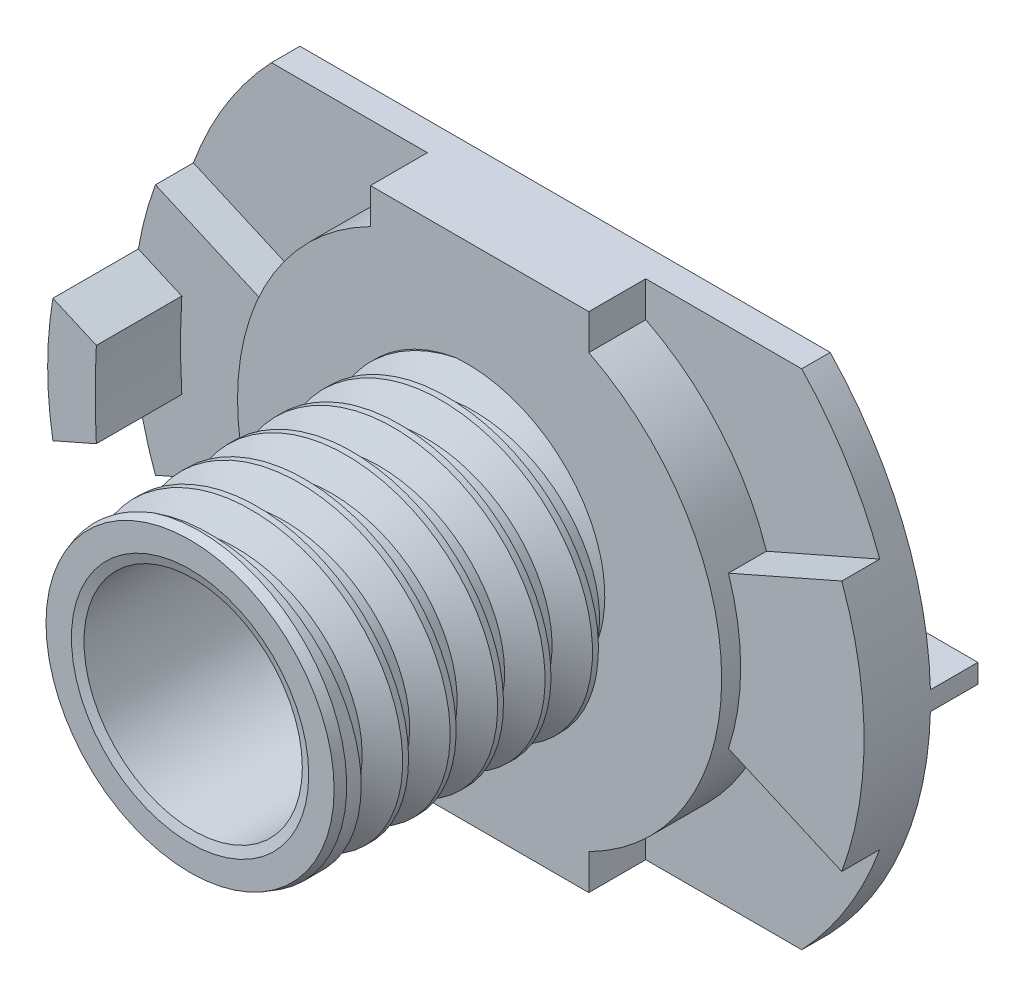
SolidWorks part; units mm, degrees
ref_plane "Front Plane" through (0, 0, 0) normal (0, 0, 1) x (1, 0, 0)
ref_plane "Top Plane" through (0, 0, 0) normal (0, 1, 0) x (1, 0, 0)
ref_plane "Right Plane" through (0, 0, 0) normal (1, 0, 0) x (0, 0, -1)
sketch "Sketch1" plane through (0, 0, 0) normal (0, 0, 1) x (1, 0, 0)
  line L1 (-5.5857, 5.3) -> (5.5857, 5.3)
  line L3 (-5.5857, -5.3) -> (5.5857, -5.3)
  line L5 (-5.5857, 5.3) -> (5.5857, -5.3) construction
  line L6 (-5.5857, -5.3) -> (5.5857, 5.3) construction
  arc A0 (-5.5857, 5.3) -> (-5.5857, -5.3) centre (0, 0) ccw
  arc A1 (5.5857, -5.3) -> (5.5857, 5.3) centre (0, 0) ccw
  dimension "D1" = 15.4
  dimension "D2" = 10.6
extrude "Boss-Extrude1" add sketch "Sketch1" along normal mid plane 0.6
sketch "Sketch2" plane through (0, 0, 0) normal (0, 0, 1) x (1, 0, 0)
  line L0 (5.5857, 5.3) -> (-5.5857, 5.3) construction
  line L1 (-2.3, 5.3) -> (2.3, 5.3)
  line L2 (-2.3, 5.3) -> (-2.3, 4.5519)
  line L4 (2.3, 5.3) -> (2.3, 4.5519)
  line L5 (-5.5857, -5.3) -> (5.5857, -5.3) construction
  line L6 (2.3, -5.3) -> (-2.3, -5.3)
  line L7 (2.3, -5.3) -> (2.3, -4.5519)
  line L9 (-2.3, -5.3) -> (-2.3, -4.5519)
  arc A0 (-2.3, 4.5519) -> (-2.3, -4.5519) centre (0, 0) ccw
  arc A1 (2.3, -4.5519) -> (2.3, 4.5519) centre (0, 0) ccw
  point P1 (0, 5.3)
  point P17 (0, -5.3)
  dimension "D1" = 10.2
  dimension "D2" = 4.6
extrude "Boss-Extrude2" add sketch "Sketch2" along normal blind 1.2 from surface starting at face at (0, 0, 0.3)
sketch "Sketch3" plane through (0, 0, 0) normal (0, 0, 1) x (1, 0, 0)
  line L0 (4.8425, 1.6) -> (7.2296, 2.65)
  line L1 (4.8425, -1.6) -> (7.2296, -2.65)
  line L2 (-4.8425, 1.6) -> (-7.2296, 2.65)
  line L3 (-4.8425, -1.6) -> (-7.2296, -2.65)
  line L4 (0, 0) -> (5.1, 0) construction
  line L5 (4.8425, 1.6) -> (4.8425, 0) construction
  line L6 (4.8425, 0) -> (4.8425, -1.6) construction
  arc A0 (2.3, -4.5519) -> (2.3, 4.5519) centre (0, 0) ccw construction
  arc A1 (5.5857, -5.3) -> (5.5857, 5.3) centre (0, 0) ccw construction
  arc A2 (-2.3, 4.5519) -> (-2.3, -4.5519) centre (0, 0) ccw construction
  arc A3 (-5.5857, 5.3) -> (-5.5857, -5.3) centre (0, 0) ccw construction
  arc A4 (-2.3, 4.5519) -> (-2.3, -4.5519) centre (0, 0) ccw construction
  arc A5 (-7.2296, 2.65) -> (-7.2296, -2.65) centre (0, 0) ccw
  arc A6 (-4.8425, 1.6) -> (-4.8425, -1.6) centre (0, 0) ccw
  arc A7 (4.8425, 1.6) -> (4.8425, -1.6) centre (0, 0) cw
  arc A8 (7.2296, 2.65) -> (7.2296, -2.65) centre (0, 0) cw
  dimension "D1" = 3.2
  dimension "D2" = 5.3
extrude "Boss-Extrude3" add sketch "Sketch3" along normal blind 0.8 from surface starting at face at (-4.2143, 0, 0.3)
sketch "Sketch4" plane through (0, 0, 0) normal (0, 0, 1) x (1, 0, 0)
  line L0 (0, 0) -> (-7.7, 0) construction
  line L1 (-5.9974, 0) -> (-5.9974, 0.2)
  line L2 (-5.9974, 0.2) -> (-7.6974, 0.2)
  line L3 (-5.9974, 0) -> (-5.9974, -0.2)
  line L4 (-5.9974, -0.2) -> (-7.6974, -0.2)
  line L5 (0, 0) -> (7.7, 0) construction
  line L6 (5.9974, 0) -> (5.9974, 0.2)
  line L7 (5.9974, 0.2) -> (7.6974, 0.2)
  line L8 (5.9974, 0) -> (5.9974, -0.2)
  line L9 (5.9974, -0.2) -> (7.6974, -0.2)
  arc A0 (-5.5857, 5.3) -> (-5.5857, -5.3) centre (0, 0) ccw construction
  arc A1 (5.5857, -5.3) -> (5.5857, 5.3) centre (0, 0) ccw construction
  arc A2 (7.6974, 0.2) -> (7.6974, -0.2) centre (0, 0) cw
  arc A3 (-7.6974, 0.2) -> (-7.6974, -0.2) centre (0, 0) ccw
  dimension "D1" = 0.2
  dimension "D2" = 1.7
extrude "Boss-Extrude4" add sketch "Sketch4" against normal blind 1 from surface contours A2 L7 L6 L8 L9 | L2 A3 L4 L3 L1 region at (-6.8483, 0, 0) region at (6.8483, 0, 0) starting at face at (0, 0, -0.3)
sketch "Sketch5" plane through (0, 0, 0) normal (0, 0, 1) x (1, 0, 0)
  circle A0 centre (0, 0) radius 3.1
  dimension "D1" = 6.2
extrude "Boss-Extrude5" add sketch "Sketch5" along normal blind 7.6 and the other way blind 1.6
sketch "Sketch6" plane through (0, 0, 0) normal (0, 0, 1) x (1, 0, 0)
  circle A0 centre (0, 0) radius 2.3
  circle A1 centre (0, 0) radius 3.1 construction
  dimension "D1" = 0.8
extrude "Cut-Extrude1" cut sketch "Sketch6" against normal up to next from surface starting at face at (3.1, 0, 7.6)
thread "Thread1" pitch 1 method cut trim with end face yes profile "Thread Profile1" start angle 0, offset 0, length 0, pitch 1, diameter 6.2
ref_plane "Plane1" through (-3.1, 0, 7.6) normal (0, -1, 0) x (-1, 0, 0)
sketch "Thread Profile1" plane through (-3.1, 0, 7.6) normal (0, -1, 0) x (-1, 0, 0)
  line L0 (0, 0) -> (0, 1) construction
  line L11 (0, 0) -> (0, 0.875)
  line L12 (0, 0.875) -> (-0.5413, 0.5625)
  line L13 (-0.5413, 0.5625) -> (-0.5413, 0.3125)
  line L15 (-0.5413, 0.3125) -> (0, 0)
  line L17 (-0.5413, 0.4375) -> (0, 0.4375) construction
  point P2 (0, 0)
  dimension "Pitch" = 1
  dimension "Profile_Angle" = 60
  dimension "Profile_Land" = 0.25
  dimension "Profile_Height" = 0.5413
chamfer "Chamfer1" distance 0.2 angle 18 2 edges at (3.1, 0, 7.6) (2.3, 0, 7.6) first distance on face at (0.8935, 0.5441, 5.1315) first distance on face at (2.3, 0, 7.6)
sketch "Sketch11" plane through (0, 0, 0) normal (0, 0, 1) x (1, 0, 0)
  line L0 (-7.7, 0) -> (-5.1, 0) construction
  line L1 (-7.5895, 1.3) -> (-6.6741, 0.8974)
  line L2 (-7.5895, -1.3) -> (-6.6741, -0.8974)
  line L3 (-4.8425, -1.6) -> (-7.2296, -2.65) construction
  line L4 (-7.2296, 2.65) -> (-4.8425, 1.6) construction
  arc A0 (-7.5895, 1.3) -> (-7.5895, -1.3) centre (0, 0) ccw
  arc A1 (-7.2296, 2.65) -> (-7.2296, -2.65) centre (0, 0) ccw construction
  arc A2 (-4.8425, 1.6) -> (-4.8425, -1.6) centre (0, 0) ccw construction
  arc A3 (-6.6741, 0.8974) -> (-6.6741, -0.8974) centre (8.8617, 0) ccw
  point P11 (-7.7, 0)
  point P19 (-6.7, 0)
  dimension "D1" = 2.6
  dimension "D3" = 1
  dimension "D2" = 1
extrude "Boss-Extrude6" add sketch "Sketch11" along normal blind 1.8 from surface starting at face at (-6.218, 0, 1.1)
